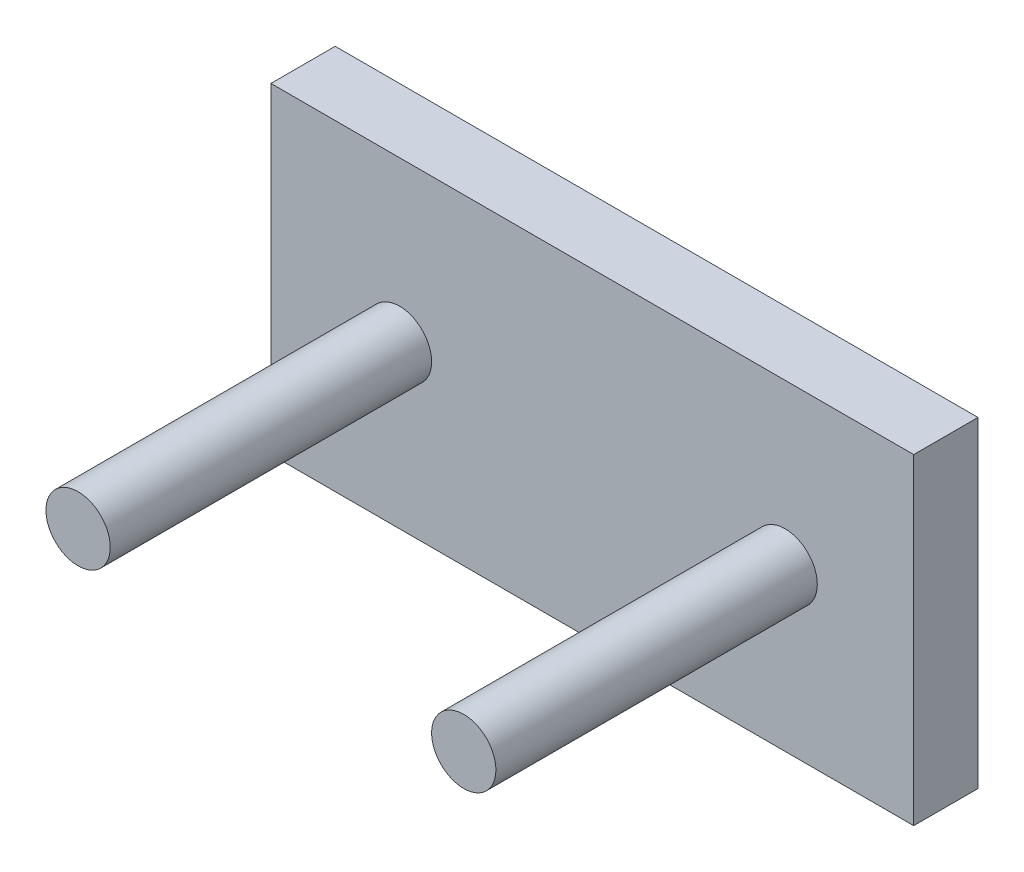
SolidWorks part; units mm, degrees
ref_plane "Front Plane" through (0, 0, 0) normal (0, 0, 1) x (1, 0, 0)
ref_plane "Top Plane" through (0, 0, 0) normal (0, 1, 0) x (1, 0, 0)
ref_plane "Right Plane" through (0, 0, 0) normal (1, 0, 0) x (0, 0, -1)
sketch "Sketch1" plane through (0, 0, 0) normal (0, 0, 1) x (1, 0, 0)
  line L1 (50, 25) -> (-50, 25)
  line L2 (50, 25) -> (50, -25)
  line L3 (50, -25) -> (-50, -25)
  line L4 (-50, 25) -> (-50, -25)
  line L5 (0, -25) -> (0, 25) construction
  line L6 (50, 0) -> (-50, 0) construction
  circle A0 centre (-30, 0) radius 5
  circle A1 centre (30, 0) radius 5
  point P0 (0, 0)
  dimension "D3" = 10
  dimension "D4" = 10
  dimension "D6" = 60
  dimension "D1" = 50
  dimension "D2" = 100
  dimension "D5" = 20
extrude "Boss-Extrude1" add sketch "Sketch1" along normal blind 10 contours A0 | A1 | L1 L4 L3 L2 A1 A0 region at (0, 0, 0) region at (-30, 0, 0) region at (30, 0, 0)
extrude "Boss-Extrude2" add sketch "Sketch1<3>" along normal blind 60 contours A0 | A1
sketch "Sketch1<3>" plane through (0, 0, 0) normal (0, 0, 1) x (1, 0, 0) same geometry as "Sketch1"
